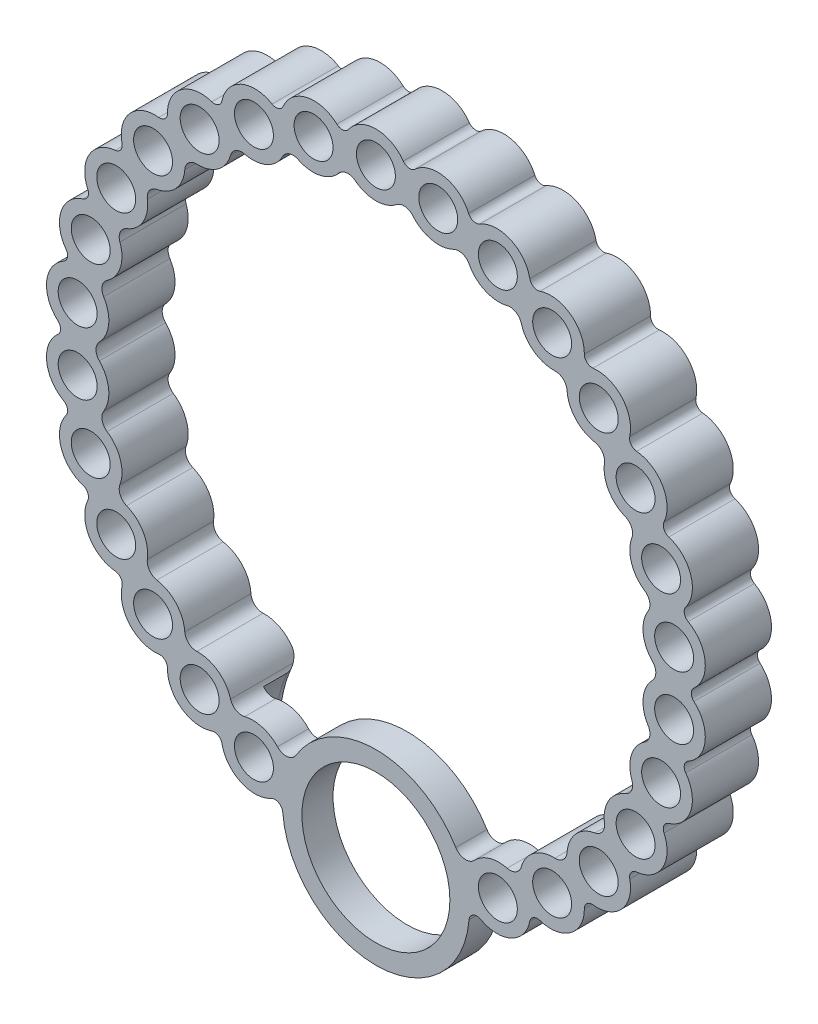
SolidWorks part; units mm, degrees
note: '?' marks a value the reader was unsure of.
ref_plane "Front Plane" through (0, 0, 0) normal (1, 0, 0) x (0, 1, 0)
ref_plane "Top Plane" through (0, 0, 0) normal (0, 0, 1) x (0, 1, 0)
ref_plane "Right Plane" through (0, 0, 0) normal (0, 1, 0) x (-1, 0, 0)
ref_axis "x axis" through (-88.99, 0, 0) along (1, 0, 0)?
ref_axis "y xxis" through (0, 88.99, 0) along (0, -1, 0)?
ref_axis "z axis" through (0, 0, 55) along (0, 0, -1)?
sketch "Sketch1" plane through (0, 0, 0) normal (0, 0, 1) x (0, 1, 0)
  line L0 (-77, 0) -> (0, 0) construction
  circle A0 centre (0, 0) radius 77 construction
  circle A1 centre (-77, 0) radius 40 construction
  circle A2 centre (-77, 0) radius 19 construction
  dimension "D1" = 80
  dimension "D2" = 38
  dimension "D3" = 77
sketch "Sketch5" plane through (0, 0, 0) normal (0, 0, 1) x (0, 1, 0)
  arc A0 (-59.026, 35.7342) -> (-75.026, 39.9513) centre (-77, 0) ccw
  circle A2 centre (0, 0) radius 85
  arc A3 (-75.026, -39.9513) -> (-75.026, 39.9513) centre (0, 0) ccw
  circle A4 centre (0, 0) radius 69
  arc A5 (-59.026, -35.7342) -> (-59.026, 35.7342) centre (0, 0) ccw
  circle A7 centre (-77, 0) radius 40
  arc A8 (-75.026, -39.9513) -> (-59.026, -35.7342) centre (-77, 0) ccw
  dimension "D1" = 8
  dimension "D2" = 8
  dimension "D3" = 0
extrude "Boss-Extrude3" add sketch "Sketch5" along normal blind 9
sketch "Sketch6" plane through (0, 0, 9) normal (0, 0, 1) x (1, 0, 0)
  arc A1 (-23.5402, -81.6753) -> (23.5402, -81.6753) centre (0, -77) ccw
  circle A2 centre (0, -77) radius 19
  circle A3 centre (0, -77) radius 19
  circle A8 centre (0, -77) radius 24 construction
  arc A9 (21.1601, -65.6753) -> (-21.1601, -65.6753) centre (0, -77) ccw
  arc A12 (39.9513, -75.026) -> (-39.9513, -75.026) centre (0, 0) ccw
  arc A13 (-35.7342, -59.026) -> (-39.9513, -75.026) centre (0, -77) ccw
  arc A14 (35.7342, -59.026) -> (-35.7342, -59.026) centre (0, 0) ccw
  arc A15 (39.9513, -75.026) -> (35.7342, -59.026) centre (0, -77) ccw
  arc A16 (23.5402, -81.6753) -> (-23.5402, -81.6753) centre (0, 0) ccw
  arc A18 (21.1601, -65.6753) -> (-21.1601, -65.6753) centre (0, 0) ccw
  dimension "D2" = 5
  dimension "D1" = 0
  dimension "D3" = 0
extrude "Boss-Extrude4" add sketch "Sketch6" along normal offset from surface (8 mm away) 17 up to face at (0, 5.0972, 0)
fillet "Fillet1" radius 3 2 edges at (38.6791, -66.8055, 0) (-38.6791, -66.8055, 0)
sketch "Sketch7" plane through (0, 0, 17) normal (0, 0, 1) x (1, 0, 0)
  line L0 (0, 85) -> (0, 69) construction
  line L1 (0, 0) -> (0, 77) construction
  line L2 (0, 0) -> (16.0092, 75.3174) construction
  arc A0 (23.5402, -81.6753) -> (-23.5402, -81.6753) centre (0, 0) ccw construction
  arc A1 (21.1601, -65.6753) -> (-21.1601, -65.6753) centre (0, 0) ccw construction
  circle A2 centre (0, 77) radius 5
  circle A3 centre (16.0092, 75.3174) radius 5
  circle A4 centre (31.3187, 70.343) radius 5
  circle A5 centre (45.2595, 62.2943) radius 5
  circle A6 centre (57.2222, 51.5231) radius 5
  circle A7 centre (66.684, 38.5) radius 5
  circle A8 centre (73.2314, 23.7943) radius 5
  circle A9 centre (76.5782, 8.0487) radius 5
  circle A10 centre (76.5782, -8.0487) radius 5
  circle A11 centre (73.2314, -23.7943) radius 5
  circle A12 centre (66.684, -38.5) radius 5
  circle A13 centre (57.2222, -51.5231) radius 5
  circle A14 centre (45.2595, -62.2943) radius 5
  circle A15 centre (31.3187, -70.343) radius 5
  circle A16 centre (16.0092, -75.3174) radius 5 [skipped]
  circle A17 centre (0, -77) radius 5 [skipped]
  circle A18 centre (-16.0092, -75.3174) radius 5 [skipped]
  circle A19 centre (-31.3187, -70.343) radius 5
  circle A20 centre (-45.2595, -62.2943) radius 5
  circle A21 centre (-57.2222, -51.5231) radius 5
  circle A22 centre (-66.684, -38.5) radius 5
  circle A23 centre (-73.2314, -23.7943) radius 5
  circle A24 centre (-76.5782, -8.0487) radius 5
  circle A25 centre (-76.5782, 8.0487) radius 5
  circle A26 centre (-73.2314, 23.7943) radius 5
  circle A27 centre (-66.684, 38.5) radius 5
  circle A28 centre (-57.2222, 51.5231) radius 5
  circle A29 centre (-45.2595, 62.2943) radius 5
  circle A30 centre (-31.3187, 70.343) radius 5
  circle A31 centre (-16.0092, 75.3174) radius 5
  dimension "D1" = 10
  dimension "D3" = 12
  dimension "D2" = 30
extrude "Cut-Extrude1" cut sketch "Sketch7" against normal up to surface (17 mm away) up to face at (0, 5.9071, 0)
sketch "Sketch8" plane through (0, 0, 17) normal (0, 0, 1) x (1, 0, 0)
  line L0 (0, 0) -> (0, 85) construction
  line L1 (-1.8694, 77) -> (2.7028, 77) construction
  line L2 (-8.2839, 78.8158) -> (-7.7612, 73.8432) construction
  arc A1 (8.2839, 78.8158) -> (-8.2839, 78.8158) centre (0, 76.3597) ccw
  circle A3 centre (0, 77) radius 3.5 construction
  arc A4 (7.7612, 73.8432) -> (-7.7612, 73.8432) centre (0, 77.6403) cw
  arc A5 (24.4896, 75.3712) -> (8.2839, 78.8158) centre (15.8761, 74.691) ccw
  arc A6 (22.9445, 70.6159) -> (7.7612, 73.8432) centre (16.1423, 75.9437) cw
  arc A7 (39.625, 68.6324) -> (24.4896, 75.3712) centre (31.0583, 69.758) ccw
  arc A8 (37.125, 64.3023) -> (22.9445, 70.6159) centre (31.5792, 70.928) cw
  arc A9 (53.0285, 58.8942) -> (39.625, 68.6324) centre (44.8831, 61.7763) ccw
  arc A10 (49.6829, 55.1784) -> (37.125, 64.3023) centre (45.6358, 62.8123) cw
  arc A11 (64.1145, 46.5819) -> (53.0285, 58.8942) centre (56.7463, 51.0946) ccw
  arc A12 (60.0694, 43.643) -> (49.6829, 55.1784) centre (57.698, 51.9515) cw
  arc A13 (72.3984, 32.2338) -> (64.1145, 46.5819) centre (66.1294, 38.1798) ccw
  arc A14 (67.8307, 30.2002) -> (60.0694, 43.643) centre (67.2385, 38.8202) cw
  arc A15 (77.5181, 16.477) -> (72.3984, 32.2338) centre (72.6224, 23.5964) ccw
  arc A16 (72.6274, 15.4374) -> (67.8307, 30.2002) centre (73.8403, 23.9922) cw
  arc A17 (79.2499, 0) -> (77.5181, 16.477) centre (75.9414, 7.9818) ccw
  arc A18 (74.2499, 0) -> (72.6274, 15.4374) centre (77.215, 8.1156) cw
  arc A19 (77.5181, -16.477) -> (79.2499, 0) centre (75.9414, -7.9818) ccw
  arc A20 (72.6274, -15.4374) -> (74.2499, 0) centre (77.215, -8.1156) cw
  arc A21 (72.3984, -32.2338) -> (77.5181, -16.477) centre (72.6224, -23.5964) ccw
  arc A22 (67.8307, -30.2002) -> (72.6274, -15.4374) centre (73.8403, -23.9922) cw
  arc A23 (64.1145, -46.5819) -> (72.3984, -32.2338) centre (66.1294, -38.1798) ccw
  arc A24 (60.0694, -43.643) -> (67.8307, -30.2002) centre (67.2385, -38.8202) cw
  arc A25 (53.0285, -58.8942) -> (64.1145, -46.5819) centre (56.7463, -51.0946) ccw
  arc A26 (49.6829, -55.1784) -> (60.0694, -43.643) centre (57.698, -51.9515) cw
  arc A27 (39.625, -68.6324) -> (53.0285, -58.8942) centre (44.8831, -61.7763) ccw
  arc A28 (37.125, -64.3023) -> (49.6829, -55.1784) centre (45.6358, -62.8123) cw
  arc A29 (24.4896, -75.3712) -> (39.625, -68.6324) centre (31.0583, -69.758) ccw
  arc A30 (22.9806, -70.0796) -> (37.125, -64.3023) centre (31.5792, -70.928) cw
  arc A31 (8.2839, -78.8158) -> (24.4896, -75.3712) centre (15.8761, -74.691) ccw [skipped]
  arc A32 (8.4135, -72.0811) -> (21.6319, -69.2714) centre (16.1423, -75.9437) cw [skipped]
  arc A33 (-8.2839, -78.8158) -> (8.2839, -78.8158) centre (0, -76.3597) ccw [skipped]
  arc A34 (-6.7569, -72.2552) -> (6.7569, -72.2552) centre (0, -77.6403) cw [skipped]
  arc A35 (-24.4896, -75.3712) -> (-8.2839, -78.8158) centre (-15.8761, -74.691) ccw [skipped]
  arc A36 (-21.6319, -69.2714) -> (-8.4135, -72.0811) centre (-16.1423, -75.9437) cw [skipped]
  arc A37 (-39.625, -68.6324) -> (-24.4896, -75.3712) centre (-31.0583, -69.758) ccw
  arc A38 (-37.125, -64.3023) -> (-22.9806, -70.0796) centre (-31.5792, -70.928) cw
  arc A39 (-53.0285, -58.8942) -> (-39.625, -68.6324) centre (-44.8831, -61.7763) ccw
  arc A40 (-49.6829, -55.1784) -> (-37.125, -64.3023) centre (-45.6358, -62.8123) cw
  arc A41 (-64.1145, -46.5819) -> (-53.0285, -58.8942) centre (-56.7463, -51.0946) ccw
  arc A42 (-60.0694, -43.643) -> (-49.6829, -55.1784) centre (-57.698, -51.9515) cw
  arc A43 (-72.3984, -32.2338) -> (-64.1145, -46.5819) centre (-66.1294, -38.1798) ccw
  arc A44 (-67.8307, -30.2002) -> (-60.0694, -43.643) centre (-67.2385, -38.8202) cw
  arc A45 (-77.5181, -16.477) -> (-72.3984, -32.2338) centre (-72.6224, -23.5964) ccw
  arc A46 (-72.6274, -15.4374) -> (-67.8307, -30.2002) centre (-73.8403, -23.9922) cw
  arc A47 (-79.2499, 0) -> (-77.5181, -16.477) centre (-75.9414, -7.9818) ccw
  arc A48 (-74.2499, 0) -> (-72.6274, -15.4374) centre (-77.215, -8.1156) cw
  arc A49 (-77.5181, 16.477) -> (-79.2499, 0) centre (-75.9414, 7.9818) ccw
  arc A50 (-72.6274, 15.4374) -> (-74.2499, 0) centre (-77.215, 8.1156) cw
  arc A51 (-72.3984, 32.2338) -> (-77.5181, 16.477) centre (-72.6224, 23.5964) ccw
  arc A52 (-67.8307, 30.2002) -> (-72.6274, 15.4374) centre (-73.8403, 23.9922) cw
  arc A53 (-64.1145, 46.5819) -> (-72.3984, 32.2338) centre (-66.1294, 38.1798) ccw
  arc A54 (-60.0694, 43.643) -> (-67.8307, 30.2002) centre (-67.2385, 38.8202) cw
  arc A55 (-53.0285, 58.8942) -> (-64.1145, 46.5819) centre (-56.7463, 51.0946) ccw
  arc A56 (-49.6829, 55.1784) -> (-60.0694, 43.643) centre (-57.698, 51.9515) cw
  arc A57 (-39.625, 68.6324) -> (-53.0285, 58.8942) centre (-44.8831, 61.7763) ccw
  arc A58 (-37.125, 64.3023) -> (-49.6829, 55.1784) centre (-45.6358, 62.8123) cw
  arc A59 (-24.4896, 75.3712) -> (-39.625, 68.6324) centre (-31.0583, 69.758) ccw
  arc A60 (-22.9445, 70.6159) -> (-37.125, 64.3023) centre (-31.5792, 70.928) cw
  arc A61 (-8.2839, 78.8158) -> (-24.4896, 75.3712) centre (-15.8761, 74.691) ccw
  arc A62 (-7.7612, 73.8432) -> (-22.9445, 70.6159) centre (-16.1423, 75.9437) cw
  arc A63 (-23.8757, -74.5607) -> (23.8757, -74.5607) centre (0, -77) ccw
  arc A64 (-24.4896, -75.3712) -> (-23.8757, -74.5607) centre (-31.0583, -69.758) ccw
  arc A65 (24.4896, -75.3712) -> (23.8757, -74.5607) centre (31.0583, -69.758) cw
  arc A66 (22.9806, -70.0796) -> (-22.9806, -70.0796) centre (0, -77) ccw
  arc A67 (21.1601, -65.6753) -> (-21.1601, -65.6753) centre (0, -77) ccw construction
  circle A70 centre (0, 0) radius 13.6069
  circle A71 centre (0, 0) radius 110.04
  point P17 (0, 85)
  point P191 (0, 0)
  arc M33 (-21.1601, -65.6753) -> (21.1601, -65.6753) centre (0, 0) cw
  arc M36 (-23.5402, -81.6753) -> (23.5402, -81.6753) centre (0, -77) ccw
  arc M37 (23.5402, -81.6753) -> (-23.5402, -81.6753) centre (0, 0) ccw
  dimension "D1" = 30
  dimension "D3" = 5
  dimension "D2" = 8
extrude "Cut-Extrude2" cut sketch "Sketch8" against normal blind 40 contours A71 M36 M37 | A64 A37 A63 M37 | A39 A37 M37 | A41 A39 M37 | A43 A41 M37 | A44 A42 M33 | A42 A40 M33 | A40 A38 M33 | A66 A38 M33 | A66 A30 M33 | A30 A28 M33 | A29 A65 A63 M37 | A29 A27 M37 | A27 A25 M37 | A28 A26 M33 | A26 A24 M33 | A25 A23 M37 | A23 A21 M37 | A21 A19 M37 | A24 A22 M33 | A22 A20 M33 | A19 A17 M37 | A20 A18 M33 | A18 A16 M33 | A16 A14 M33 | A15 A13 M37 | A17 A15 M37 | A14 A12 M33 | A12 A10 M33 | A11 A9 M37 | A13 A11 M37 | A9 A7 M37 | A10 A8 M33 | A8 A6 M33 | A7 A5 M37 | A5 A1 M37 | A6 A4 M33 | A4 A62 M33 | A62 A60 M33 | A61 A59 M37 | A61 A1 M37 | A59 A57 M37 | A60 A58 M33 | A58 A56 M33 | A57 A55 M37 | A55 A53 M37 | A53 A51 M37 | A56 A54 M33 | A54 A52 M33 | A52 A50 M33 | A45 A43 M37 | A47 A45 M37 | A49 A47 M37 | A51 A49 M37 | A50 A48 M33 | A48 A46 M33 | A46 A44 M33
fillet "Fillet2" radius 3 28 edges at (-7.7612, 73.8432, 8.5) (-22.9445, 70.6159, 8.5) (-37.125, 64.3023, 8.5) (7.7612, 73.8432, 8.5) (-49.6829, 55.1784, 8.5) (-60.0694, 43.643, 8.5) (-67.8307, 30.2002, 8.5) (-72.6274, 15.4374, 8.5) (-74.2499, 0, 8.5) (-72.6274, -15.4374, 8.5) (-67.8307, -30.2002, 8.5) (22.9806, -70.0796, 13) (-22.9806, -70.0796, 13) (-60.0694, -43.643, 8.5) (-49.6829, -55.1784, 8.5) (-37.125, -64.3023, 13) (67.8307, -30.2002, 8.5) (72.6274, -15.4374, 8.5) (60.0694, -43.643, 8.5) (49.6829, -55.1784, 8.5) (37.125, -64.3023, 13) (74.2499, 0, 8.5) (72.6274, 15.4374, 8.5) (67.8307, 30.2002, 8.5) (60.0694, 43.643, 8.5) (49.6829, 55.1784, 8.5) (37.125, 64.3023, 8.5) (22.9445, 70.6159, 8.5)
fillet "Fillet3" radius 2 28 edges at (23.8757, -74.5607, 13) (39.625, -68.6324, 9.1717) (53.0285, -58.8942, 8.5) (64.1145, -46.5819, 8.5) (72.3984, -32.2338, 8.5) (77.5181, -16.477, 8.5) (79.2499, 0, 8.5) (77.5181, 16.477, 8.5) (72.3984, 32.2338, 8.5) (64.1145, 46.5819, 8.5) (53.0285, 58.8942, 8.5) (39.625, 68.6324, 8.5) (24.4896, 75.3712, 8.5) (8.2839, 78.8158, 8.5) (-8.2839, 78.8158, 8.5) (-24.4896, 75.3712, 8.5) (-39.625, 68.6324, 8.5) (-53.0285, 58.8942, 8.5) (-64.1145, 46.5819, 8.5) (-77.5181, -16.477, 8.5) (-72.3984, 32.2338, 8.5) (-77.5181, 16.477, 8.5) (-79.2499, 0, 8.5) (-72.3984, -32.2338, 8.5) (-64.1145, -46.5819, 8.5) (-53.0285, -58.8942, 8.5) (-39.625, -68.6324, 9.1717) (-23.8757, -74.5607, 13)
